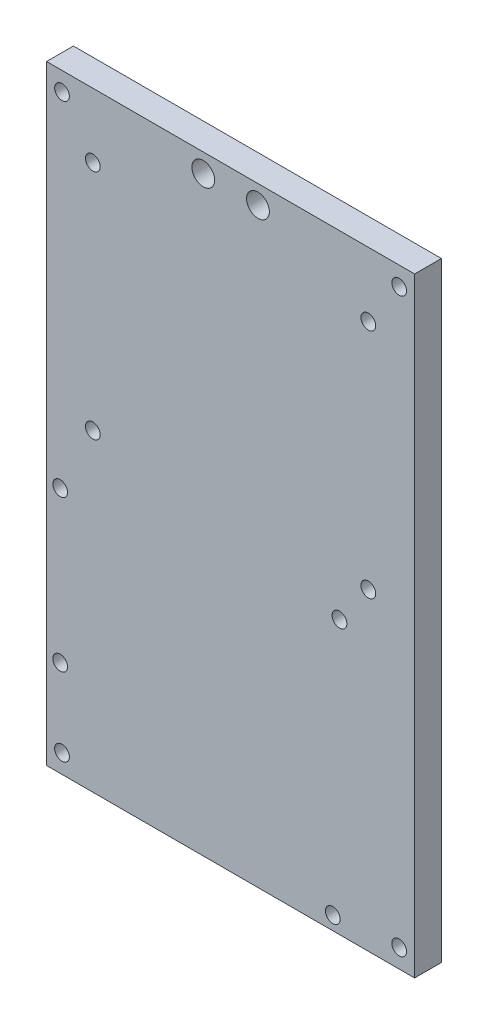
SolidWorks part; units mm, degrees
ref_plane "Front" through (0, 0, 0) normal (0, 0, 1) x (1, 0, 0)
ref_plane "Top" through (0, 0, 0) normal (0, 1, 0) x (1, 0, 0)
ref_plane "Right" through (0, 0, 0) normal (1, 0, 0) x (0, 0, -1)
sketch "arduinoOutline" plane through (0, 0, 0) normal (0, 0, 1) x (1, 0, 0)
  line L0 (0, 32.73) -> (2.54, 35.27) construction
  line L2 (0, 0) -> (0, 32.73) construction
  line L5 (2.54, 35.27) -> (2.54, 36.81) construction
  line L6 (3.54, 37.81) -> (67.6, 37.81) construction
  line L7 (68.6, 36.81) -> (68.6, -14.59) construction
  line L8 (67.6, -15.59) -> (4.06, -15.59) construction
  line L9 (4.06, -15.59) -> (2.54, -14.07) construction
  line L10 (2.54, -14.07) -> (2.54, -2.54) construction
  line L11 (2.54, -2.54) -> (0, 0) construction
  arc A0 (2.54, 36.81) -> (3.54, 37.81) centre (3.54, 36.81) cw construction
  arc A1 (68.6, -14.59) -> (67.6, -15.59) centre (67.6, -14.59) cw construction
  arc A2 (67.6, 37.81) -> (68.6, 36.81) centre (67.6, 36.81) cw construction
  point P8 (2.54, 37.81)
  point P13 (68.6, -15.59)
  point P16 (68.6, 37.81)
  dimension "D6" = 1
  dimension "D9" = 1
  dimension "D10" = 1
  dimension "D1" = 32.73
  dimension "D2" = 135
  dimension "D3" = 3.5921
  dimension "D4" = 2.54
  dimension "D5" = 66.06
  dimension "D7" = 53.4
  dimension "D8" = 64.54
  dimension "D11" = 135
  dimension "D12" = 2.1496
  dimension "D13" = 11.53
  dimension "D14" = 135
  dimension "D15" = 3.5921
sketch "arduinoMountingHolesSketch" plane through (0, 0, 0) normal (0, 0, 1) x (1, 0, 0)
  line L0 (0, 0) -> (0, 32.73) construction
  line L1 (67.6, -15.59) -> (4.06, -15.59) construction
  line L2 (3.54, 37.81) -> (67.6, 37.81) construction
  line L3 (68.6, 36.81) -> (68.6, -14.59) construction
  circle A0 centre (2.54, 2.28) radius 1.375
  circle A1 centre (2.54, 30.45) radius 1.375
  circle A2 centre (54.6, 35.27) radius 1.375
  circle A3 centre (53.35, -13.05) radius 1.375
  dimension "D9" = 2.75
  dimension "D1" = 2.54
  dimension "D2" = 17.87
  dimension "D3" = 2.54
  dimension "D4" = 7.36
  dimension "D5" = 2.54
  dimension "D6" = 14
  dimension "D7" = 2.54
  dimension "D8" = 15.25
sketch "9VbatteryMountingHolesSketch" plane through (0, 0, 0) normal (0, 0, 1) x (1, 0, 0)
  line L0 (0, 16.365) -> (68.6, 16.365) construction
  line L1 (4.875, 40.31) -> (63.725, 40.31) construction
  line L2 (4.875, 40.31) -> (4.875, 88.56) construction
  line L3 (4.875, 88.56) -> (63.725, 88.56) construction
  line L4 (63.725, 40.31) -> (63.725, 88.56) construction
  line L5 (0, 0) -> (0, 32.73) construction
  line L6 (68.6, 36.81) -> (68.6, -14.59) construction
  line L7 (34.3, 40.31) -> (34.3, 88.56) construction
  line L8 (4.875, 64.435) -> (63.725, 64.435) construction
  line L10 (3.54, 37.81) -> (67.6, 37.81) construction
  circle A0 centre (8.625, 86.06) radius 1.375
  circle A1 centre (59.975, 86.06) radius 1.375
  circle A2 centre (8.625, 42.81) radius 1.375
  circle A3 centre (59.975, 42.81) radius 1.375
  point P4 (34.3, 16.365)
  point P5 (34.3, 88.56)
  dimension "D3" = 2.75
  dimension "D1" = 48.25
  dimension "D2" = 58.85
  dimension "D4" = 2.5
  dimension "D5" = 3.75
  dimension "D6" = 2.5
sketch "legBracketMountingHolesSketch" plane through (0, 0, 0) normal (0, 0, 1) x (1, 0, 0)
  line L0 (34.3, 91.06) -> (34.3, 98.06) construction
  line L1 (24.1051, 98.06) -> (44.4949, 98.06) construction
  line L2 (24.1051, 98.06) -> (24.1051, 91.06) construction
  line L3 (24.1051, 91.06) -> (44.4949, 91.06) construction
  line L4 (44.4949, 98.06) -> (44.4949, 91.06) construction
  circle A0 centre (29.2026, 94.56) radius 2.125
  circle A1 centre (39.3974, 94.56) radius 2.125
  point P4 (24.1051, 94.56)
  point P5 (34.3, 98.06)
  dimension "D4" = 4.25
  dimension "D1" = 7
  dimension "D2" = 20.3898
  dimension "D3" = 2.5
  dimension "D5" = 5.0974
sketch "backsideMountingHolesSketch" plane through (0, 0, 0) normal (0, 0, 1) x (1, 0, 0)
  line L0 (0, 41.235) -> (68.6, 41.235) construction
  line L9 (0, 0) -> (0, 32.73) construction
  line L10 (34.3, 40.31) -> (34.3, 88.56) construction
  line L11 (68.6, 36.81) -> (68.6, -14.59) construction
  line L12 (24.1051, 98.06) -> (44.4949, 98.06) construction
  line L13 (4.875, 88.56) -> (63.725, 88.56) construction
  line L14 (4.875, 40.31) -> (4.875, 88.56) construction
  circle A1 centre (2.875, 94.56) radius 1.375
  circle A5 centre (65.725, 94.56) radius 1.375
  circle A6 centre (65.725, -12.09) radius 1.375
  circle A7 centre (2.875, -12.09) radius 1.375
  dimension "D1" = 2.75
  dimension "D2" = 56.825
  dimension "D3" = 6
  dimension "D4" = 2
sketch "Sketch1" plane through (0, 0, 0) normal (0, 0, 1) x (1, 0, 0)
  line L0 (67.6, -15.59) -> (4.06, -15.59) construction
  line L1 (0, 98.06) -> (68.6, 98.06)
  line L2 (0, 98.06) -> (0, -15.59)
  line L3 (0, -15.59) -> (68.6, -15.59)
  line L4 (68.6, 98.06) -> (68.6, -15.59)
  line L5 (0, 0) -> (0, 32.73) construction
  line L6 (68.6, 36.81) -> (68.6, -14.59) construction
  line L9 (24.1051, 98.06) -> (44.4949, 98.06) construction
extrude "bracketBase" add sketch "Sketch1" along normal blind 5
extrude "arduinoMountingHoles" cut sketch "arduinoMountingHolesSketch" against normal through all and the other way blind 22
extrude "9VbatteryMountingHoles" cut sketch "9VbatteryMountingHolesSketch" along normal blind 20
extrude "legBracketMountingHoles" cut sketch "legBracketMountingHolesSketch" along normal blind 13
extrude "backsideMountingHoles" cut sketch "backsideMountingHolesSketch" along normal blind 24
equation "\"D2@backsideMountingHolesSketch\"=113.65mm/2"
